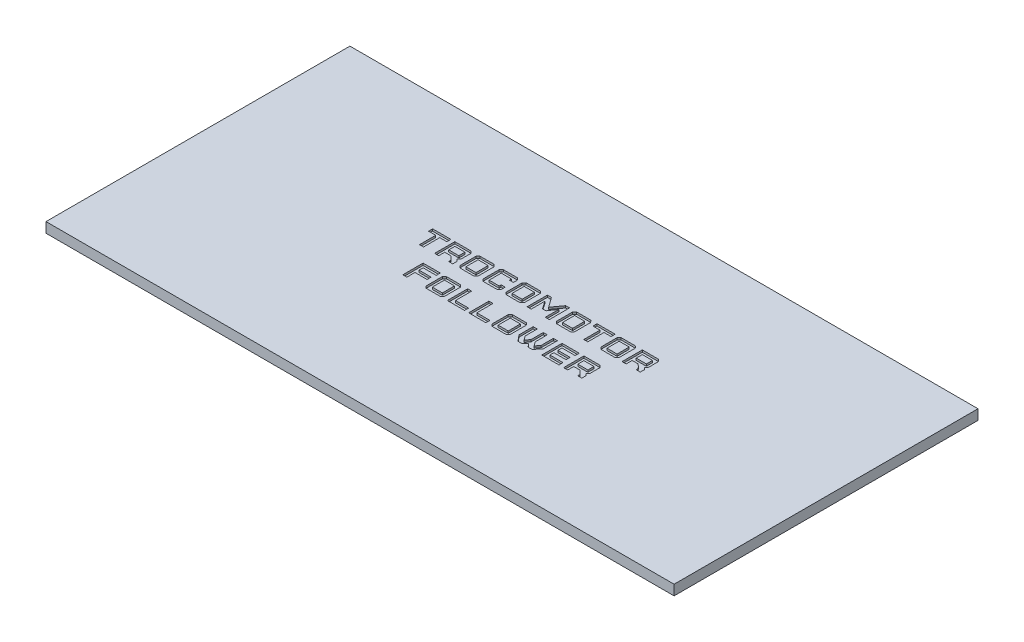
SolidWorks part; units mm, degrees
ref_plane "Front Plane" through (0, 0, 0) normal (0, 0, 1) x (1, 0, 0)
ref_plane "Top Plane" through (0, 0, 0) normal (0, 1, 0) x (1, 0, 0)
ref_plane "Right Plane" through (0, 0, 0) normal (1, 0, 0) x (0, 0, -1)
sketch "Sketch1" plane through (0, 0, 0) normal (0, 1, 0) x (1, 0, 0)
  line L1 (-155, 75) -> (155, 75)
  line L2 (-155, 75) -> (-155, -75)
  line L3 (-155, -75) -> (155, -75)
  line L4 (155, 75) -> (155, -75)
  line L5 (-155, 75) -> (155, -75) construction
  line L6 (-155, -75) -> (155, 75) construction
  point P0 (0, 0)
  dimension "D1" = 150
  dimension "D2" = 310
extrude "Boss-Extrude1" add sketch "Sketch1" along normal blind 5
sketch "Sketch2" plane through (0, 5, 0) normal (0, 1, 0) x (1, 0, 0)
  line L0 (-155, 7.3111) -> (155, 7.3111) construction
  line L1 (155, -75) -> (155, 75) construction
  text T0 "Trocomotor\r\nFollower" font "Furore" height 10
  point P5 (0, 7.3111)
extrude "Cut-Extrude1" cut sketch "Sketch2" against normal blind 1
